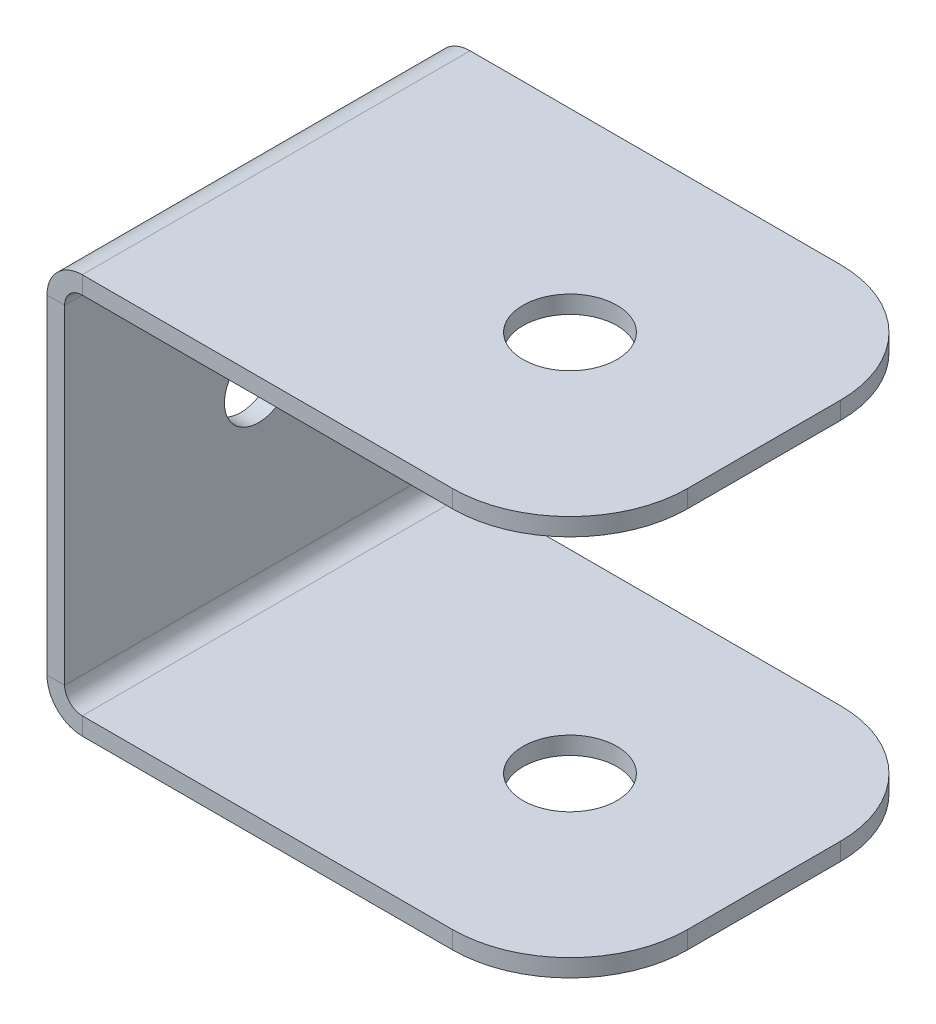
SolidWorks part; units mm, degrees
note: The reader was unsure of these and kept them because the rebuilt part matched: bend radius of "BaseBend1", "BaseBend2".
material "AISI 316 Stainless Steel Sheet (SS)"
ref_plane "Front Plane" through (0, 0, 0) normal (0, 0, 1) x (1, 0, 0)
ref_plane "Top Plane" through (0, 0, 0) normal (0, 1, 0) x (1, 0, 0)
ref_plane "Right Plane" through (0, 0, 0) normal (1, 0, 0) x (0, 0, -1)
sketch "Sketch1" plane through (0, 0, 0) normal (0, 0, 1) x (1, 0, 0)
  line L0 (43, 15.5) -> (0, 15.5)
  line L1 (0, 15.5) -> (0, -15.5)
  line L2 (0, -15.5) -> (43, -15.5)
  line L3 (10, 0) -> (43, 0) construction
  line L4 (43, 15.5) -> (43, 0) construction
  dimension "D1" = 31
  dimension "D2" = 33
  dimension "D3" = 10
base flange "Base-Flange1" sketch "Sketch1" end condition mid plane depth 33 reverse direction no thickness 1.5 reverse thickness direction no bend radius 1.5
bend "BaseBend1" bend radius 1.5 bend angle 90 parameters "D5"=1
bend "BaseBend2" bend radius 1.5 bend angle 90 parameters "D5"=2
sketch "Sketch6" plane through (0, 17, 0) normal (0, 1, 0) x (1, 0, 0)
  line L0 (10, 0) -> (43, 0) construction
  line L1 (43, 0) -> (26.5, 0) construction
  line L2 (43, -16.5) -> (43, 16.5) construction
  circle A0 centre (26.5, 0) radius 16.5 construction
  circle A1 centre (26.5, 0) radius 4
  dimension "D1" = 33
  dimension "D2" = 8
extrude "Cut-Extrude1" cut sketch "Sketch6" against normal through all normal cut yes
hole_wizard "M5 Clearance Hole1" positions "Sketch8" profile "Sketch9" hole size "M5" standard "ISO" end condition through all
sketch "Sketch8" plane through (-1.5, 0, 0) normal (-1, 0, 0) x (0, 0, 1)
  point P0 (0, 0)
sketch "Sketch9" plane through (-1.5, 0, 0) normal (0, 1, 0) x (0, 0, 1)
  line L0 (0, 0) -> (0, 44.5)
  line L1 (0, 44.5) -> (2.9, 44.5)
  line L2 (2.9, 44.5) -> (2.9, 0)
  line L5 (2.9, 0) -> (0, 0)
  line L11 (0, -6.35) -> (0, 107.95) construction
  dimension "Thru Hole Dia." = 5.8
  dimension "Thru Hole Depth" = 44.5
fillet "Fillet1" radius 10 4 edges at (43, -16.25, 16.5) (43, -16.25, -16.5) (43, 16.25, -16.5) (43, 16.25, 16.5)
sketch "Bend-Lines1" [suppressed] plane through (0, 0, 0) normal (0, 1, 0) x (1, 0, 0)
sketch "Bounding-Box1" [suppressed] plane through (0, 0, 0) normal (0, 1, 0) x (1, 0, 0)
sheet metal parameters "Sheet-Metal1" thickness 1.5 parameters "D1"=1.5
flat pattern "Flat-Pattern1" [suppressed]
sketch "Bend-Lines2" plane through (0, -15.5, 0) normal (0, 1, 0) x (1, 0, 0)
  line L0 (-31.8014, -20) -> (-31.8014, 20) construction
  line L1 (-0.2671, -20) -> (-0.2671, 20) construction
  line L2 (-31.8014, -20) -> (-31.8014, 20) construction
  line L3 (-0.2671, -20) -> (-0.2671, 20) construction
sketch3d "Bounding-Box2" [suppressed]
  line L0 (53, 0, 0) -> (-85.0686, 0, 0) construction
  line L1 (53, 40, 0) -> (-85.0686, 40, 0) construction
  line L2 (53, 0, 0) -> (53, 40, 0) construction
  line L3 (-85.0686, 0, 0) -> (-85.0686, 40, 0) construction
bend of the flat pattern "Flatten-<BaseBend1>1"
bend of the flat pattern "Flatten-<BaseBend2>1"
sheet metal parameters "Sheet-Metal2" thickness 1.5 parameters "D1"=1.5
flat pattern "Flat-Pattern1"
sketch "Bend-Lines2" plane through (0, -15.5, 0) normal (0, 1, 0) x (1, 0, 0)
  line L0 (-31.8014, -16.5) -> (-31.8014, 16.5) construction
  line L1 (-0.2671, -16.5) -> (-0.2671, 16.5) construction
  line L2 (-31.8014, -16.5) -> (-31.8014, 16.5) construction
  line L3 (-0.2671, -16.5) -> (-0.2671, 16.5) construction
sketch3d "Bounding-Box2" [suppressed]
  line L0 (53, 0, 0) -> (-85.0686, 0, 0) construction
  line L1 (53, 33, 0) -> (-85.0686, 33, 0) construction
  line L2 (53, 0, 0) -> (53, 33, 0) construction
  line L3 (-85.0686, 0, 0) -> (-85.0686, 33, 0) construction
bend of the flat pattern "Flatten-<BaseBend1>1"
bend of the flat pattern "Flatten-<BaseBend2>1"
sheet metal parameters "Sheet-Metal3" thickness 1.5 parameters "D1"=1.5
flat pattern "Flat-Pattern1"
sketch "Bend-Lines2" plane through (0, -15.5, 0) normal (0, 1, 0) x (1, 0, 0)
  line L0 (-31.8014, -16.5) -> (-31.8014, 16.5) construction
  line L1 (-0.2671, -16.5) -> (-0.2671, 16.5) construction
  line L2 (-31.8014, -16.5) -> (-31.8014, 16.5) construction
  line L3 (-0.2671, -16.5) -> (-0.2671, 16.5) construction
sketch3d "Bounding-Box2" [suppressed]
  line L0 (43, 33, 0) -> (-75.0686, 33, 0) construction
  line L1 (43, 0, 0) -> (-75.0686, 0, 0) construction
  line L2 (43, 33, 0) -> (43, 0, 0) construction
  line L3 (-75.0686, 33, 0) -> (-75.0686, 0, 0) construction
bend of the flat pattern "Flatten-<BaseBend1>1"
bend of the flat pattern "Flatten-<BaseBend2>1"
